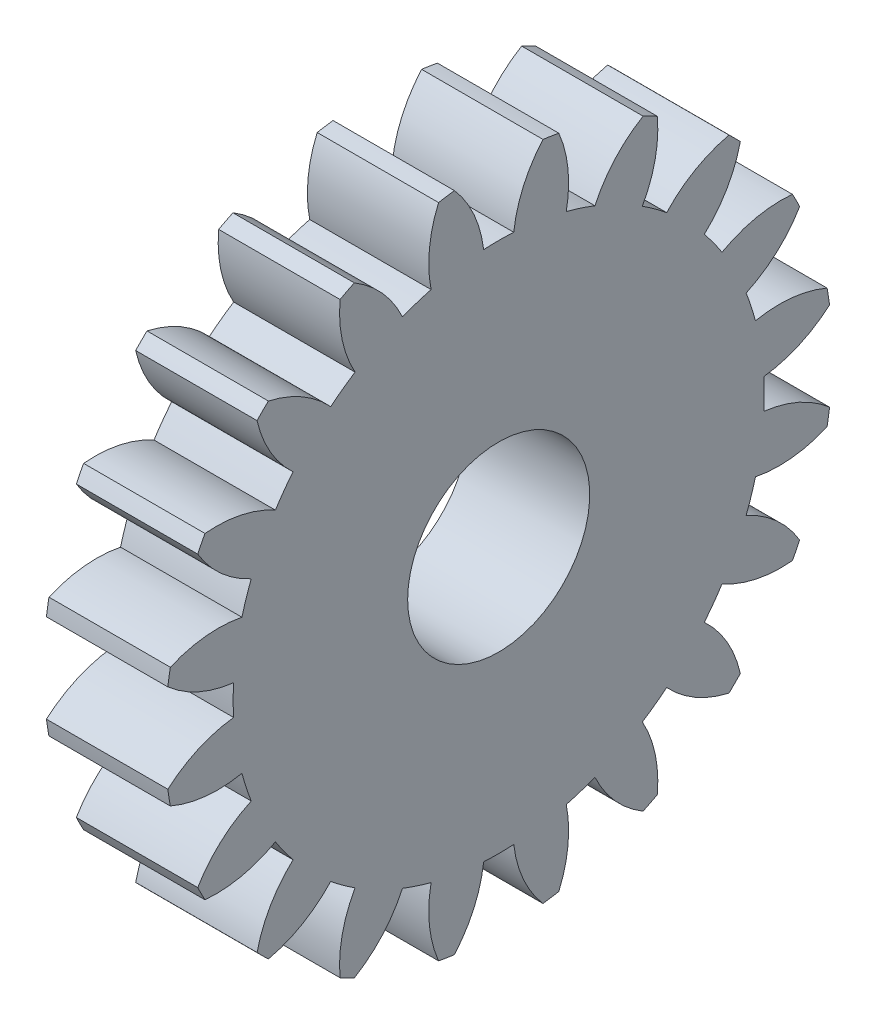
SolidWorks part; units mm, degrees
ref_plane "Plane1" through (0, 0, 0) normal (0, 0, 1) x (1, 0, 0)
ref_plane "Plane2" through (0, 0, 0) normal (0, 1, 0) x (1, 0, 0)
ref_plane "Plane3" through (0, 0, 0) normal (1, 0, 0) x (0, 0, -1)
sketch "HoldingSke" plane through (0, 0, 0) normal (0, 1, 0) x (1, 0, 0)
  line L0 (0, 0) -> (0.6265, -0.228)
  line L1 (-15, 0) -> (100, 0) construction
  line L2 (0, 0) -> (-2.1039, 2.3779)
  line L3 (0, 0) -> (-11.863, 4.5341)
  line L4 (0, 0) -> (8.1152, 2.9537)
  line L5 (0, 0) -> (-46.8476, -17.4728)
  line L6 (0, 0) -> (-4.9738, -3.3558)
  line L7 (-2.1039, 2.3779) -> (8.6586, 51.2059)
  line L8 (-76.2, 54.61) -> (-74.8, 54.61)
  line L9 (-71.009, 38.7566) -> (-53.1078, 45.2721)
  line L10 (-76.2, 71.12) -> (104.1128, 71.12)
  line L11 (0, 0) -> (-6, 0)
  line L12 (-76.2, 101.6) -> (-76.147, 101.6)
  line L13 (24.9733, 27.94) -> (52.9518, 28.4284)
  line L14 (24.9733, 27.94) -> (24.9743, 27.94)
  line L15 (24.9733, 27.94) -> (100.4006, 29.5858)
  line L16 (-63.627, -1.5) -> (-12.827, -1.5)
  circle A0 centre (0, 0) radius 4.5
  circle A1 centre (0, 0) radius 13.124
  circle A2 centre (0, 0) radius 37.5
  circle A3 centre (0, 0) radius 4.5
  dimension "Num_teeth" = 20
  dimension "Pitch_radius" = 180.3128
  dimension "Width" = 6
  dimension "Thickness" = 6
sketch "BasProSke" plane through (0, 0, 0) normal (0, 1, 0) x (1, 0, 0)
  line L0 (-10, 0) -> (60, 0) construction
  line L1 (0, 0) -> (0, 16.5)
  line L2 (0, 0) -> (6, 0)
  line L3 (6, 0) -> (6, 16.5)
  line L4 (6, 16.5) -> (0, 16.5)
  dimension "Thickness" = 6
  dimension "Diameter" = 33
revolve "Base-Revolve" add sketch "BasProSke" angle 360 about L0
sketch "TooCutSke" plane through (0, 0, 0) normal (1, 0, 0) x (0, 0, -1)
  line L1 (0, 0) -> (0, 107) construction
  line L2 (0, 0) -> (-1.2696, 14.9462) construction
  line L3 (0, 0) -> (-4.6808, 29.5532) construction
  line L4 (-1.2696, 14.9462) -> (-2.3404, 14.7766) construction
  arc A0 (0.7438, 13.1029) -> (-0.7438, 13.1029) centre (0, 0) ccw
  arc A1 (2.21, 16.377) -> (-2.21, 16.377) centre (0, 0) ccw
  circle A2 centre (0, 0) radius 15 construction
  circle A3 centre (0, 0) radius 14.0954 construction
  arc A4 (-0.7438, 13.1029) -> (-2.21, 16.377) centre (-6.7025, 12.3999) ccw
  arc A5 (2.21, 16.377) -> (0.7438, 13.1029) centre (6.7025, 12.3999) ccw
extrude "ToothCut" cut sketch "TooCutSke" along normal through all
fillet "Breaks" [suppressed] radius 0.03 tangent propagation no
fillet "RootFillets" [suppressed] radius 0.376
pattern_circular "TeethCuts" count 20 every 18 about axis through (-10, 0, 0) along (1, 0, 0) of "ToothCut", "RootFillets", "Breaks"
sketch "HubNeaOneSke" plane through (0, 0, 0) normal (-1, 0, 0) x (0, 0, 1)
  circle A0 centre (0, 0) radius 13.124
  dimension "Diameter" = 26.248
extrude "HubNearOne" [suppressed] add sketch "HubNeaOneSke" along normal blind 44.0001
sketch "HubNeaBotSke" plane through (0, 0, 0) normal (-1, 0, 0) x (0, 0, 1)
  circle A0 centre (0, 0) radius 13.124
  dimension "Diameter" = 26.248
extrude "HubNearBoth" [suppressed] add sketch "HubNeaBotSke" along normal blind 22
ref_plane "FarPln" through (6, 0, 0) normal (1, 0, 0) x (0, 0, -1)
sketch "HubFarSke" plane through (6, 0, 0) normal (1, 0, 0) x (0, 0, -1)
  circle A0 centre (0, 0) radius 13.124
  dimension "Diameter" = 26.248
extrude "HubFar" [suppressed] add sketch "HubFarSke" along normal blind 22
sketch "BorSke" plane through (0, 0, 0) normal (1, 0, 0) x (0, 0, -1)
  circle A0 centre (0, 0) radius 4.5
  dimension "Diameter" = 9
extrude "Bore" cut sketch "BorSke" along normal mid plane 100.0001
sketch "KeySke" plane through (0, 0, 0) normal (1, 0, 0) x (0, 0, -1)
  line L0 (-1.5, 0) -> (-1.5, 5.9)
  line L1 (-1.5, 5.9) -> (1.5, 5.9)
  line L2 (1.5, 5.9) -> (1.5, 0)
  line L3 (0, 0) -> (0, 34) construction
  line L4 (-1.5, 0) -> (1.5, 0)
  dimension "Width" = 3
extrude "Keyway" [suppressed] cut sketch "KeySke" along normal mid plane 100.0001
pattern_circular "Keyway2" [suppressed] count 2 every 90 about axis through (-10, 0, 0) along (1, 0, 0)
sketch "Esquisse1" plane through (6, 0, 0) normal (1, 0, 0) x (0, 0, -1)
  circle A0 centre (0, 0) radius 15
  dimension "D1" = 30
equation "' \"Module@HoldingSke\" = 6.35"
equation "' \"Num_teeth@HoldingSke\" = 12"
equation "' \"Ap@HoldingSke\" =  20"
equation "' \"Ap@HoldingSke\" = 20"
equation "' \"Width@HoldingSke\" = 0.5 * 25.4"
equation "' \"Hub_dia@HoldingSke\"= 1 * 25.4"
equation "' \"Hub_dia@HoldingSke\" = 1 * 25.4"
equation "' \"Overall_len@HoldingSke\" = 1.0 * 25.4"
equation "' \"Bore@HoldingSke\" = 0.75 * 25.4"
equation "' \"T_dim@HoldingSke\" = 0.1 * 25.4"
equation "' \"Width@KeySke\" = 0.25 * 25.4"
equation "' \"Show_teeth@HoldingSke\" = 13"
equation "' \"Backlash@HoldingSke\" = 0.009 * 25.4"
equation "' \"Addendum_fac@HoldingSke\" = 1.0"
equation "' \"Dedendum_fac@HoldingSke\" = 1.25"
equation "' \"Dedendum_add@HoldingSke\" = 0.00005 * 25.4"
equation "' \"Clearance_fac@HoldingSke\" = 0.25"
equation "\"Pitch@HoldingSke\" = 1 / \"Module@HoldingSke\""
equation "\"Overcut_dia@TooCutSke\" = (\"Num_teeth@HoldingSke\" + 2 * \"Addendum_fac@HoldingSke\") / \"Pitch@HoldingSke\" + 0.002 * 25.4"
equation "\"Pitch_dia@TooCutSke\" = \"Num_teeth@HoldingSke\" / \"Pitch@HoldingSke\""
equation "\"Base_dia@TooCutSke\" = \"Num_teeth@HoldingSke\" / \"Pitch@HoldingSke\" * cos((\"Ap@HoldingSke\"  * 3.14159265 / 180))"
equation "\"Root_dia@TooCutSke\" = (\"Num_teeth@HoldingSke\" + 2) / \"Pitch@HoldingSke\" - 2 * (\"Addendum_fac@HoldingSke\" + \"Dedendum_fac@HoldingSke\") / \"Pitch@HoldingSke\" - \"Dedendum_add@HoldingSke\" * 2"
equation "\"Half_ang@TooCutSke\" = 180 / \"Num_teeth@HoldingSke\""
equation "\"Half_CT@TooCutSke\" = \"Num_teeth@HoldingSke\" / \"Pitch@HoldingSke\" * sin((3.14159265 / 2 / \"Num_teeth@HoldingSke\")) / 2 - 7 * \"Backlash@HoldingSke\" / 4"
equation "\"Flank_rad@TooCutSke\" = \"Num_teeth@HoldingSke\" / \"Pitch@HoldingSke\" / 5"
equation "\"Radius@RootFillets\" = \"Clearance_fac@HoldingSke\" / \"Pitch@HoldingSke\" + \"Dedendum_add@HoldingSke\""
equation "\"Break_rad@Breaks\" = 0.02 / \"Pitch@HoldingSke\""
equation "\"Thickness@HoldingSke\" = \"Width@HoldingSke\""
equation "\"OAL@HoldingSke\" = \"Thickness@HoldingSke\""
equation "\"MHD@HoldingSke\" = (\"Num_teeth@HoldingSke\" + 2) / \"Pitch@HoldingSke\" - 2 * (\"Addendum_fac@HoldingSke\" + \"Dedendum_fac@HoldingSke\")  / \"Pitch@HoldingSke\" - \"Dedendum_add@HoldingSke\" * 2"
equation "\"MBD@HoldingSke\" = (\"Num_teeth@HoldingSke\" + 2) / \"Pitch@HoldingSke\" - 2 * (\"Addendum_fac@HoldingSke\" + \"Dedendum_fac@HoldingSke\")  / \"Pitch@HoldingSke\" - \"Dedendum_add@HoldingSke\" * 2 - 0.002 * 25.4"
equation "\"MHD@HoldingSke\" = ((sgn( \"MHD@HoldingSke\" - \"Hub_dia@HoldingSke\" )-1)*( \"MHD@HoldingSke\" - \"Hub_dia@HoldingSke\" ))/-2+ \"Hub_dia@HoldingSke\""
equation "\"MBD@HoldingSke\" = ((sgn( \"MBD@HoldingSke\" - \"Bore@HoldingSke\" )-1)*( \"MBD@HoldingSke\" - \"Bore@HoldingSke\" ))/-2+ \"Bore@HoldingSke\""
equation "\"OAL@HoldingSke\" = ((sgn( \"OAL@HoldingSke\" - \"Overall_len@HoldingSke\" )+1)*( \"OAL@HoldingSke\" - \"Overall_len@HoldingSke\" ))/2 + \"Overall_len@HoldingSke\" + 0.000002 * 25.4"
equation "\"Num_teeth@TeethCuts\" = int( \"Show_teeth@HoldingSke\" ) + 1"
equation "\"Num_teeth@TeethCuts\" = ((sgn( \"Num_teeth@TeethCuts\" - \"Num_teeth@HoldingSke\" )-1)*( \"Num_teeth@TeethCuts\" - \"Num_teeth@HoldingSke\" ))/-2+ \"Num_teeth@HoldingSke\""
equation "\"Num_teeth@TeethCuts\" = ((sgn( \"Num_teeth@TeethCuts\" - 2.0)+1)*( \"Num_teeth@TeethCuts\" - 2.0))/2 +2.0"
equation "\"Angle@TeethCuts\" = 360.0 / \"Num_teeth@HoldingSke\""
equation "\"Diameter@BasProSke\" = (\"Num_teeth@HoldingSke\" + 2 * \"Addendum_fac@HoldingSke\") / \"Pitch@HoldingSke\""
equation "\"Thickness@BasProSke\"  = \"Thickness@HoldingSke\""
equation "' \"Fillet_rad@BasProSke\" =  \"Thickness@HoldingSke\" * 0.05"
equation "' \"Fillet_rad@BasProSke\" = \"Thickness@HoldingSke\" * 0.05"
equation "\"MHD@HoldingSke\" = ((sgn( \"MHD@HoldingSke\" - \"Root_dia@TooCutSke\" )-1)*( \"MHD@HoldingSke\" - \"Root_dia@TooCutSke\" ))/-2+ \"Root_dia@TooCutSke\""
equation "\"Diameter@HubNeaOneSke\" = \"MHD@HoldingSke\""
equation "\"Length@HubNearOne\" = \"OAL@HoldingSke\" - \"Thickness@BasProSke\""
equation "\"Diameter@HubNeaBotSke\" = \"MHD@HoldingSke\""
equation "\"Length@HubNearBoth\" = ( \"OAL@HoldingSke\" - \"Thickness@BasProSke\" ) / 2.0"
equation "\"Thickness@FarPln\" = \"Thickness@BasProSke\""
equation "\"Diameter@HubFarSke\" = \"MHD@HoldingSke\""
equation "\"Length@HubFar\" = ( \"OAL@HoldingSke\" - \"Thickness@BasProSke\" ) / 2.0"
equation "\"Diameter@BorSke\" = \"MBD@HoldingSke\""
equation "\"D1@Bore\" = \"OAL@HoldingSke\" * 2.0"
equation "\"D1@Keyway\" = \"OAL@HoldingSke\" * 2.0"
equation "\"Offset@KeySke\" = \"T_dim@HoldingSke\" + \"MBD@HoldingSke\" / 2.0"
